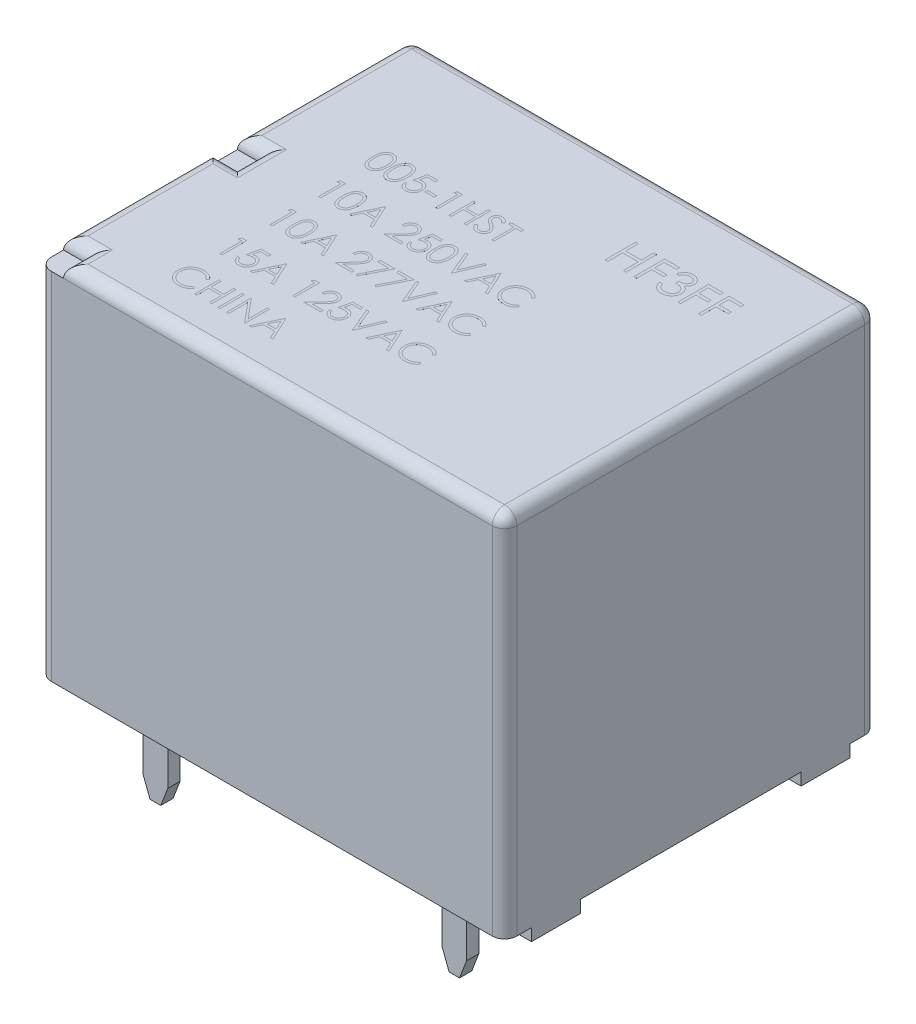
SolidWorks part; units mm, degrees
ref_plane "Front Plane" through (0, 0, 0) normal (0, 0, 1) x (1, 0, 0)
ref_plane "Top Plane" through (0, 0, 0) normal (0, 1, 0) x (1, 0, 0)
ref_plane "Right Plane" through (0, 0, 0) normal (1, 0, 0) x (0, 0, -1)
sketch "Sketch1" plane through (0, 0, 0) normal (0, 1, 0) x (1, 0, 0)
  line L1 (-9.5, -7.6) -> (9.5, -7.6)
  line L2 (-9.5, -7.6) -> (-9.5, 7.6)
  line L3 (-9.5, 7.6) -> (9.5, 7.6)
  line L4 (9.5, -7.6) -> (9.5, 7.6)
  line L5 (0, 7.6) -> (0, -7.6) construction
  line L6 (-9.5, 0) -> (9.5, 0) construction
  point P0 (0, 0)
extrude "Boss-Extrude1" add sketch "Sketch1" along normal blind 15
sketch "Sketch2" plane through (0, 0, 0) normal (0, -1, 0) x (1, 0, 0)
  line L0 (-9.5, -7.6) -> (-9.5, 7.6) construction
  line L1 (-9.5, -6.5) -> (-8.75, -6.5)
  line L2 (-9.5, -6.5) -> (-9.5, -4.5)
  line L3 (-9.5, -4.5) -> (-8.75, -4.5)
  line L4 (-8.75, -6.5) -> (-8.75, -4.5)
  line L5 (-9.5, 0) -> (9.5, 0) construction
  line L6 (9.5, 7.6) -> (9.5, -7.6) construction
  line L7 (0, 7.6) -> (0, -7.6) construction
  line L8 (-9.5, 7.6) -> (9.5, 7.6) construction
  line L9 (9.5, -7.6) -> (-9.5, -7.6) construction
  line L10 (-8.75, 6.5) -> (-8.75, 4.5)
  line L11 (-9.5, 4.5) -> (-8.75, 4.5)
  line L12 (-9.5, 6.5) -> (-9.5, 4.5)
  line L13 (-9.5, 6.5) -> (-8.75, 6.5)
  line L14 (9.5, 6.5) -> (8.75, 6.5)
  line L15 (9.5, 6.5) -> (9.5, 4.5)
  line L16 (9.5, 4.5) -> (8.75, 4.5)
  line L17 (8.75, 6.5) -> (8.75, 4.5)
  line L18 (8.75, -6.5) -> (8.75, -4.5)
  line L19 (9.5, -4.5) -> (8.75, -4.5)
  line L20 (9.5, -6.5) -> (9.5, -4.5)
  line L21 (9.5, -6.5) -> (8.75, -6.5)
  point P6 (-9.125, -6.5)
  dimension "D1" = 2
  dimension "D2" = 0.75
  dimension "D3" = 6.5
extrude "Boss-Extrude2" add sketch "Sketch2" along normal blind 0.5
sketch "Sketch4" plane through (0, 15, 0) normal (0, 1, 0) x (1, 0, 0)
  line L0 (-9.5, 7.6) -> (-9.5, -7.6) construction
  line L1 (-8.5, -0.5) -> (-9.5, -0.5)
  line L2 (-8.5, -0.5) -> (-8.5, 0.5)
  line L3 (-8.5, 0.5) -> (-9.5, 0.5)
  line L4 (-9.5, -0.5) -> (-9.5, 0.5)
  line L5 (-9, 0.5) -> (-9, -0.5) construction
  line L6 (-8.5, 0) -> (-9.5, 0) construction
  line L7 (-9.5, -7.6) -> (9.5, -7.6) construction
  line L8 (-8.5, -6.6) -> (-9.5, -6.6)
  line L9 (-8.5, -6.6) -> (-8.5, -7.6)
  line L10 (-8.5, -7.6) -> (-9.5, -7.6)
  line L11 (-9.5, -6.6) -> (-9.5, -7.6)
  line L12 (-9, -7.6) -> (-9, -6.6) construction
  line L13 (-8.5, -7.1) -> (-9.5, -7.1) construction
  point P0 (-9, 0)
  point P6 (-9, -7.1)
extrude "Cut-Extrude1" cut sketch "Sketch4" against normal blind 0.5
fillet "Fillet1" radius 0.5 14 edges at (9.5, 7.5, 7.6) (9.5, 7.5, -7.6) (9.5, 15, 0) (0, 15, -7.6) (-9.5, 7.5, -7.6) (-9.5, 15, -4.05) (0.5, 15, 7.6) (-9.5, 7.25, 7.6) (-9, 15, -0.5) (-8.5, 15, 0) (-9, 15, 0.5) (-9.5, 15, 3.55) (-9, 15, 6.6) (-8.5, 15, 7.1)
sketch "Sketch3" plane through (0, 0, 0) normal (0, -1, 0) x (1, 0, 0)
  line L0 (-9.5, 0) -> (9.5, 0) construction
  line L1 (-8.25, -0.501) -> (-7.95, -0.501)
  line L2 (-8.25, -0.501) -> (-8.25, 0.499)
  line L3 (-8.25, 0.499) -> (-7.95, 0.499)
  line L4 (-7.95, -0.501) -> (-7.95, 0.499)
  line L5 (-8.1, 0.499) -> (-8.1, -0.501) construction
  line L6 (-8.25, -0.001) -> (-7.95, -0.001) construction
  line L7 (-6.6071, -6.25) -> (-5.5929, -6.25)
  line L8 (-6.6071, -6.25) -> (-6.6071, -5.75)
  line L9 (-6.6071, -5.75) -> (-5.5929, -5.75)
  line L10 (-5.5929, -6.25) -> (-5.5929, -5.75)
  line L11 (-6.1, -5.75) -> (-6.1, -6.25) construction
  line L12 (-6.6071, -6) -> (-5.5929, -6) construction
  line L13 (-9.5, -4.5) -> (-9.5, 4.5) construction
  line L14 (9.5, 4.5) -> (9.5, -4.5) construction
  line L15 (-6.6071, 6) -> (-5.5929, 6) construction
  line L16 (-6.1, 5.75) -> (-6.1, 6.25) construction
  line L17 (-5.5929, 6.25) -> (-5.5929, 5.75)
  line L18 (-6.6071, 5.75) -> (-5.5929, 5.75)
  line L19 (-6.6071, 6.25) -> (-6.6071, 5.75)
  line L20 (-6.6071, 6.25) -> (-5.5929, 6.25)
  line L22 (5.6, 5.75) -> (6.6, 5.75)
  line L23 (5.6, 5.75) -> (5.6, 6.25)
  line L24 (5.6, 6.25) -> (6.6, 6.25)
  line L25 (6.6, 5.75) -> (6.6, 6.25)
  line L26 (6.1, 6.25) -> (6.1, 5.75) construction
  line L27 (5.6, 6) -> (6.6, 6) construction
  point P0 (-8.1, -0.001)
  point P4 (-6.1, -6)
  point P28 (-6.1, 6)
  point P29 (6.1, 6)
  point P37 (6.1, 6)
  dimension "D1" = 6
  dimension "D2" = 3.4
  dimension "D3" = 1
  dimension "D4" = 0.5
  dimension "D5" = 12.2
  dimension "D6" = 2
extrude "Boss-Extrude3" add sketch "Sketch3" along normal blind 3.5
chamfer "Chamfer1" distance 0.75 angle 21 8 edges at (6.6, -3.5, 6) (5.6, -3.5, 6) (-5.5929, -3.5, 6) (-6.6071, -3.5, 6) (-8.1, -3.5, 0.499) (-8.1, -3.5, -0.501) (-5.5929, -3.5, -6) (-6.6071, -3.5, -6) first distance on face at (6.6, -1.75, 6) first distance on face at (5.6, -1.75, 6) first distance on face at (-5.5929, -1.75, 6) first distance on face at (-6.6071, -1.75, 6) first distance on face at (-8.1, -1.75, 0.499) first distance on face at (-8.1, -1.75, -0.501) first distance on face at (-5.5929, -1.75, -6) first distance on face at (-6.6071, -1.75, -6)
sketch "Sketch5" plane through (0, 15, 0) normal (0, 1, 0) x (1, 0, 0)
  text T0 "HF3FF" font "Century Gothic" height 1.25
  text T1 "005-1HST" font "Century Gothic" height 1
  text T2 "10A 250VAC" font "Century Gothic" height 1
  text T3 "10A 277VAC" font "Century Gothic" height 1
  text T4 "15A 125VAC" font "Century Gothic" height 1
  text T5 "CHINA" font "Century Gothic" height 1
extrude "Boss-Extrude4" add sketch "Sketch5" along normal blind 0.0001
